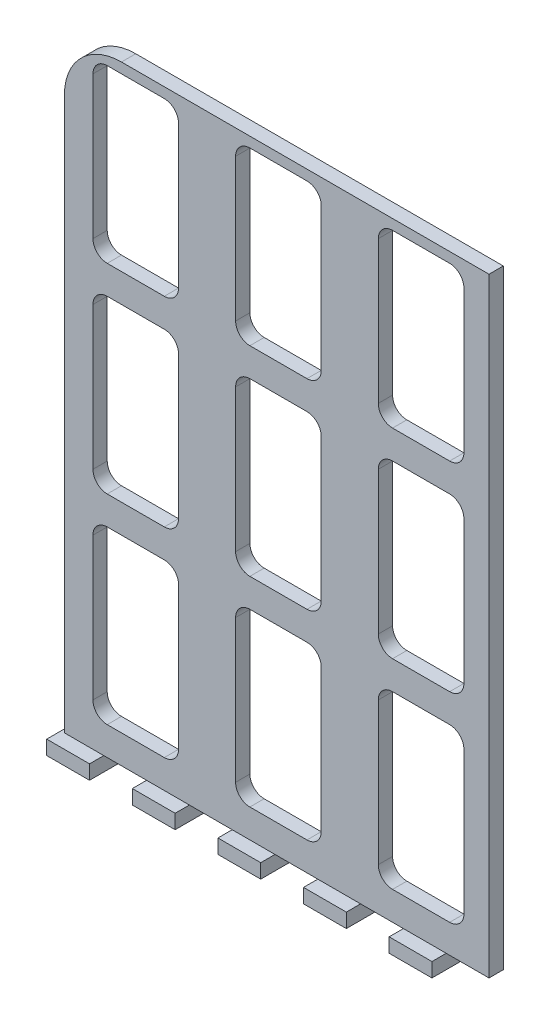
SolidWorks part; units mm, degrees
material "Balsa"
ref_plane "Front Plane" through (0, 0, 0) normal (0, 0, 1) x (1, 0, 0)
ref_plane "Top Plane" through (0, 0, 0) normal (0, 1, 0) x (1, 0, 0)
ref_plane "Right Plane" through (0, 0, 0) normal (1, 0, 0) x (0, 0, -1)
sketch "Sketch1" plane through (0, 0, 0) normal (0, 0, 1) x (1, 0, 0)
  line L0 (0, 0) -> (188.976, 0)
  line L1 (188.976, 0) -> (188.976, 271.272)
  line L2 (188.976, 271.272) -> (25.4, 271.272)
  line L3 (0, 245.872) -> (0, 0)
  arc A0 (25.4, 271.272) -> (0, 245.872) centre (25.4, 245.872) ccw
  point P8 (0, 271.272)
  point P11 (188.976, 271.272)
  dimension "D1" = 188.976
  dimension "D2" = 271.272
  dimension "D3" = 188.976
extrude "Boss-Extrude1" add sketch "Sketch1" along normal blind 6.35
sketch "Sketch2" plane through (0, 0, 6.35) normal (0, 0, 1) x (1, 0, 0)
  line L38 (76.2, 19.05) -> (76.2, 82.55)
  line L39 (19.05, 12.7) -> (44.45, 12.7)
  line L68 (12.7, 19.05) -> (12.7, 82.55)
  line L69 (19.05, 88.9) -> (44.45, 88.9)
  line L70 (50.8, 19.05) -> (50.8, 82.55)
  line L71 (82.55, 12.7) -> (107.95, 12.7)
  line L72 (114.3, 19.05) -> (114.3, 82.55)
  line L73 (82.55, 88.9) -> (107.95, 88.9)
  line L74 (139.7, 19.05) -> (139.7, 82.55)
  line L75 (146.05, 12.7) -> (171.45, 12.7)
  line L76 (177.8, 19.05) -> (177.8, 82.55)
  line L77 (146.05, 88.9) -> (171.45, 88.9)
  line L78 (76.2, 107.95) -> (76.2, 171.45)
  line L79 (82.55, 101.6) -> (107.95, 101.6)
  line L80 (114.3, 107.95) -> (114.3, 171.45)
  line L81 (82.55, 177.8) -> (107.95, 177.8)
  line L82 (139.7, 107.95) -> (139.7, 171.45)
  line L83 (146.05, 101.6) -> (171.45, 101.6)
  line L84 (177.8, 107.95) -> (177.8, 171.45)
  line L85 (146.05, 177.8) -> (171.45, 177.8)
  line L86 (76.2, 196.85) -> (76.2, 260.35)
  line L87 (82.55, 190.5) -> (107.95, 190.5)
  line L88 (114.3, 196.85) -> (114.3, 260.35)
  line L89 (82.55, 266.7) -> (107.95, 266.7)
  line L90 (139.7, 196.85) -> (139.7, 260.35)
  line L91 (146.05, 190.5) -> (171.45, 190.5)
  line L92 (177.8, 196.85) -> (177.8, 260.35)
  line L93 (146.05, 266.7) -> (171.45, 266.7)
  line L94 (12.7, 107.95) -> (12.7, 171.45)
  line L95 (19.05, 101.6) -> (44.45, 101.6)
  line L96 (50.8, 107.95) -> (50.8, 171.45)
  line L97 (19.05, 177.8) -> (44.45, 177.8)
  line L98 (12.7, 196.85) -> (12.7, 260.35)
  line L99 (19.05, 190.5) -> (44.45, 190.5)
  line L100 (50.8, 196.85) -> (50.8, 260.35)
  line L101 (19.05, 266.7) -> (44.45, 266.7)
  line L102 (0, 245.872) -> (0, 0) construction
  line L103 (0, 0) -> (188.976, 0) construction
  arc A0 (139.7, 19.05) -> (146.05, 12.7) centre (146.05, 19.05) ccw
  arc A1 (171.45, 12.7) -> (177.8, 19.05) centre (171.45, 19.05) ccw
  arc A22 (177.8, 82.55) -> (171.45, 88.9) centre (171.45, 82.55) ccw
  arc A23 (139.7, 82.55) -> (146.05, 88.9) centre (146.05, 82.55) cw
  arc A24 (76.2, 82.55) -> (82.55, 88.9) centre (82.55, 82.55) cw
  arc A25 (114.3, 82.55) -> (107.95, 88.9) centre (107.95, 82.55) ccw
  arc A26 (107.95, 12.7) -> (114.3, 19.05) centre (107.95, 19.05) ccw
  arc A27 (76.2, 19.05) -> (82.55, 12.7) centre (82.55, 19.05) ccw
  arc A28 (44.45, 12.7) -> (50.8, 19.05) centre (44.45, 19.05) ccw
  arc A29 (44.45, 88.9) -> (50.8, 82.55) centre (44.45, 82.55) cw
  arc A30 (12.7, 82.55) -> (19.05, 88.9) centre (19.05, 82.55) cw
  arc A31 (19.05, 12.7) -> (12.7, 19.05) centre (19.05, 19.05) cw
  arc A32 (12.7, 107.95) -> (19.05, 101.6) centre (19.05, 107.95) ccw
  arc A33 (12.7, 171.45) -> (19.05, 177.8) centre (19.05, 171.45) cw
  arc A34 (50.8, 171.45) -> (44.45, 177.8) centre (44.45, 171.45) ccw
  arc A35 (44.45, 101.6) -> (50.8, 107.95) centre (44.45, 107.95) ccw
  arc A36 (76.2, 107.95) -> (82.55, 101.6) centre (82.55, 107.95) ccw
  arc A37 (76.2, 171.45) -> (82.55, 177.8) centre (82.55, 171.45) cw
  arc A38 (114.3, 171.45) -> (107.95, 177.8) centre (107.95, 171.45) ccw
  arc A39 (107.95, 101.6) -> (114.3, 107.95) centre (107.95, 107.95) ccw
  arc A40 (139.7, 107.95) -> (146.05, 101.6) centre (146.05, 107.95) ccw
  arc A41 (171.45, 101.6) -> (177.8, 107.95) centre (171.45, 107.95) ccw
  arc A42 (139.7, 171.45) -> (146.05, 177.8) centre (146.05, 171.45) cw
  arc A43 (177.8, 171.45) -> (171.45, 177.8) centre (171.45, 171.45) ccw
  arc A44 (177.8, 260.35) -> (171.45, 266.7) centre (171.45, 260.35) ccw
  arc A45 (171.45, 190.5) -> (177.8, 196.85) centre (171.45, 196.85) ccw
  arc A46 (139.7, 196.85) -> (146.05, 190.5) centre (146.05, 196.85) ccw
  arc A47 (139.7, 260.35) -> (146.05, 266.7) centre (146.05, 260.35) cw
  arc A48 (76.2, 260.35) -> (82.55, 266.7) centre (82.55, 260.35) cw
  arc A49 (114.3, 260.35) -> (107.95, 266.7) centre (107.95, 260.35) ccw
  arc A50 (107.95, 190.5) -> (114.3, 196.85) centre (107.95, 196.85) ccw
  arc A51 (76.2, 196.85) -> (82.55, 190.5) centre (82.55, 196.85) ccw
  arc A52 (12.7, 196.85) -> (19.05, 190.5) centre (19.05, 196.85) ccw
  arc A53 (44.45, 190.5) -> (50.8, 196.85) centre (44.45, 196.85) ccw
  arc A54 (50.8, 260.35) -> (44.45, 266.7) centre (44.45, 260.35) ccw
  arc A55 (12.7, 260.35) -> (19.05, 266.7) centre (19.05, 260.35) cw
  point P88 (50.8, 12.7)
  point P93 (12.7, 88.9)
  point P96 (12.7, 12.7)
  dimension "D7" = 6.35
  dimension "D1" = 76.2
  dimension "D2" = 38.1
  dimension "D3" = 3
  dimension "D4" = 3
  dimension "D5" = 12.7
  dimension "D6" = 12.7
extrude "Cut-Extrude1" cut sketch "Sketch2" along direction (0, 0, 1) on the side against the normal up to surface (6.35 mm away) contours A55 L98 A52 L99 A53 L100 A54 L101 | L95 A35 L96 A34 L97 A33 L94 A32 | L86 A51 L87 A50 L88 A49 L89 A48 | L79 A39 L80 A38 L81 A37 L78 A36 | A47 L90 A46 L91 A45 L92 A44 L93 | L84 A43 L85 A42 L82 A40 L83 A41 | A23 L74 A0 L75 A1 L76 A22 L77 | L38 A27 L71 A26 L72 A25 L73 A24 | A31 L39 A28 L70 A29 L69 A30 L68 region at (95.25, 50.8, 6.35) region at (31.75, 50.8, 6.35) region at (158.75, 50.8, 6.35) region at (95.25, 139.7, 6.35) region at (158.75, 139.7, 6.35) region at (95.25, 228.6, 6.35) region at (158.75, 228.6, 6.35) region at (31.75, 139.7, 6.35) region at (31.75, 228.6, 6.35) up to face at (79.6183, 158.7353, 0)
sketch "Sketch3" plane through (0, 0, 6.35) normal (0, 0, 1) x (1, 0, 0)
  line L0 (169.926, 0) -> (169.926, -6.35)
  line L1 (188.976, 0) -> (169.926, 0)
  line L2 (188.976, 0) -> (188.976, -6.35)
  line L3 (188.976, -6.35) -> (169.926, -6.35)
  line L4 (169.926, 0) -> (169.926, -6.35)
  line L5 (169.926, 0) -> (150.876, 0)
  line L6 (150.876, 0) -> (150.876, -6.35)
  line L7 (169.926, -6.35) -> (150.876, -6.35)
  line L8 (150.876, 0) -> (150.876, -6.35)
  line L9 (150.876, 0) -> (131.826, 0)
  line L10 (131.826, 0) -> (131.826, -6.35)
  line L11 (150.876, -6.35) -> (131.826, -6.35)
  line L12 (131.826, 0) -> (131.826, -6.35)
  line L13 (131.826, 0) -> (112.776, 0)
  line L14 (112.776, 0) -> (112.776, -6.35)
  line L15 (131.826, -6.35) -> (112.776, -6.35)
  line L16 (112.776, 0) -> (112.776, -6.35)
  line L17 (112.776, 0) -> (93.726, 0)
  line L18 (93.726, 0) -> (93.726, -6.35)
  line L19 (112.776, -6.35) -> (93.726, -6.35)
  line L20 (93.726, 0) -> (93.726, -6.35)
  line L21 (93.726, 0) -> (74.676, 0)
  line L22 (74.676, 0) -> (74.676, -6.35)
  line L23 (93.726, -6.35) -> (74.676, -6.35)
  line L24 (74.676, 0) -> (74.676, -6.35)
  line L25 (74.676, 0) -> (55.626, 0)
  line L26 (55.626, 0) -> (55.626, -6.35)
  line L27 (74.676, -6.35) -> (55.626, -6.35)
  line L28 (55.626, 0) -> (55.626, -6.35)
  line L29 (55.626, 0) -> (36.576, 0)
  line L30 (36.576, 0) -> (36.576, -6.35)
  line L31 (55.626, -6.35) -> (36.576, -6.35)
  line L32 (36.576, 0) -> (36.576, -6.35)
  line L33 (36.576, 0) -> (17.526, 0)
  line L34 (17.526, 0) -> (17.526, -6.35)
  line L35 (36.576, -6.35) -> (17.526, -6.35)
  line L36 (17.526, 0) -> (17.526, -6.35)
  line L37 (17.526, 0) -> (-1.524, 0)
  line L39 (17.526, -6.35) -> (-1.524, -6.35)
  line L72 (-1.524, 0) -> (-1.524, -6.35) [skipped]
  line L73 (-1.524, 0) -> (-1.524, -6.35) [skipped]
  line L74 (-1.524, 0) -> (-20.574, 0) [skipped]
  line L75 (-20.574, 0) -> (-20.574, -6.35) [skipped]
  line L76 (-1.524, -6.35) -> (-20.574, -6.35) [skipped]
  line L77 (-20.574, 0) -> (-20.574, -6.35) [skipped]
  line L78 (-20.574, 0) -> (-39.624, 0) [skipped]
  line L79 (-39.624, 0) -> (-39.624, -6.35) [skipped]
  line L80 (-20.574, -6.35) -> (-39.624, -6.35) [skipped]
  line L81 (-39.624, 0) -> (-39.624, -6.35) [skipped]
  line L82 (-39.624, 0) -> (-58.674, 0) [skipped]
  line L83 (-58.674, 0) -> (-58.674, -6.35) [skipped]
  line L84 (-39.624, -6.35) -> (-58.674, -6.35) [skipped]
  line L85 (-58.674, 0) -> (-58.674, -6.35) [skipped]
  line L86 (-58.674, 0) -> (-77.724, 0) [skipped]
  line L87 (-77.724, 0) -> (-77.724, -6.35) [skipped]
  line L88 (-58.674, -6.35) -> (-77.724, -6.35) [skipped]
  line L89 (-77.724, 0) -> (-77.724, -6.35) [skipped]
  line L90 (-77.724, 0) -> (-96.774, 0) [skipped]
  line L91 (-96.774, 0) -> (-96.774, -6.35) [skipped]
  line L92 (-77.724, -6.35) -> (-96.774, -6.35) [skipped]
  line L93 (-96.774, 0) -> (-96.774, -6.35) [skipped]
  line L94 (-96.774, 0) -> (-115.824, 0) [skipped]
  line L95 (-115.824, 0) -> (-115.824, -6.35) [skipped]
  line L96 (-96.774, -6.35) -> (-115.824, -6.35) [skipped]
  line L97 (-115.824, 0) -> (-115.824, -6.35) [skipped]
  line L98 (-134.874, 0) -> (-134.874, -6.35) [skipped]
  line L99 (-115.824, -6.35) -> (-134.874, -6.35) [skipped]
  line L100 (-134.874, 0) -> (-134.874, -6.35) [skipped]
  line L101 (-134.874, 0) -> (-153.924, 0) [skipped]
  line L102 (-153.924, 0) -> (-153.924, -6.35) [skipped]
  line L103 (-134.874, -6.35) -> (-153.924, -6.35) [skipped]
  line L104 (-115.824, 0) -> (-134.874, 0) [skipped]
  line L105 (-1.524, 0) -> (-1.524, -6.35)
  dimension "D1" = 6.35
  dimension "D2" = 19.05
  dimension "D3" = 18
extrude "Boss-Extrude2" add sketch "Sketch3" against normal blind 12.7 and the other way blind 6.35 contours L39 L34 | L31 L26 L30 | L23 L18 L22 | L15 L10 L14 | L7 L0 L6 region at (160.401, -3.175, 6.35) region at (122.301, -3.175, 6.35) region at (84.201, -3.175, 6.35) region at (46.101, -3.175, 6.35) region at (8.001, -3.175, 6.35)
sketch "Sketch4" plane through (188.976, 0, 0) normal (1, 0, 0) x (0, 0, -1)
  line L0 (-6.35, 0) -> (0, 0) construction
  point P0 (-3.175, 0)
